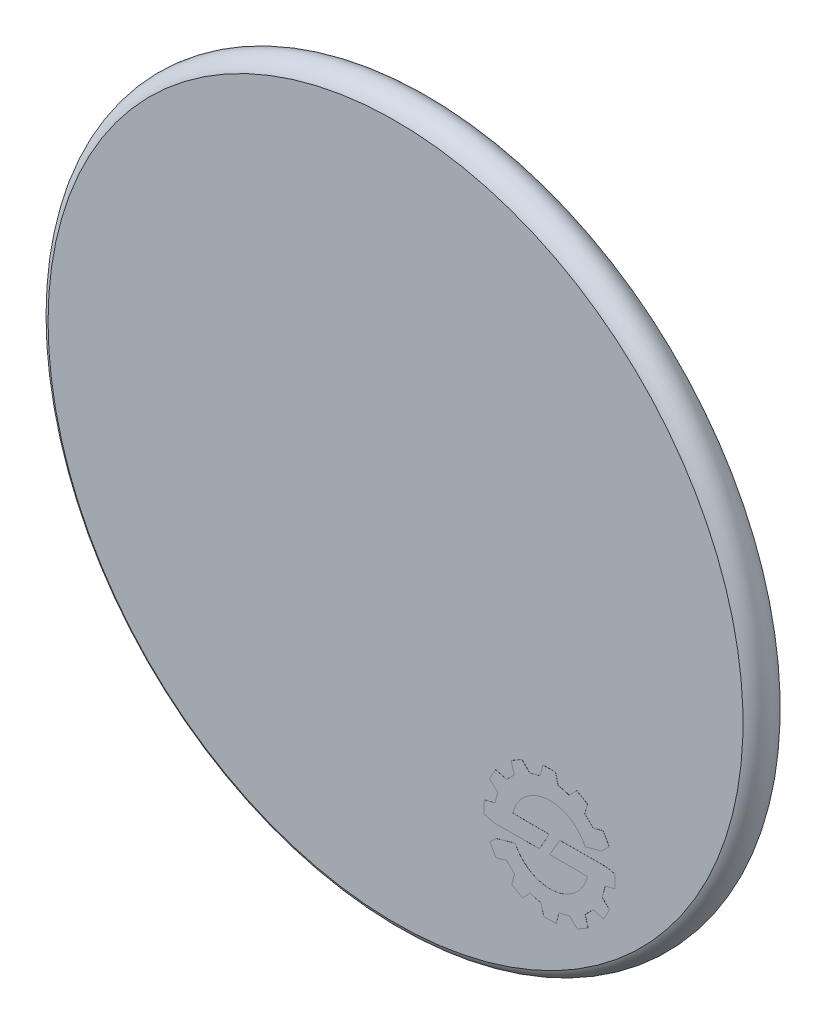
SolidWorks part; units mm, degrees
ref_plane "Front Plane" through (0, 0, 0) normal (0, 0, 1) x (1, 0, 0)
ref_plane "Top Plane" through (0, 0, 0) normal (0, 1, 0) x (1, 0, 0)
ref_plane "Right Plane" through (0, 0, 0) normal (1, 0, 0) x (0, 0, -1)
sketch "Sketch1" plane through (0, 0, 0) normal (0, 1, 0) x (1, 0, 0)
  line L0 (0, 0) -> (-40, 0)
  line L3 (-40, 0) -> (-42, 1.5)
  line L4 (0, 0) -> (0, -3)
  line L5 (0, -3) -> (-42, -3)
  line L6 (-42, -3) -> (-44.5, -3)
  line L8 (-44.5, 1.5) -> (-42, 1.5)
  arc A0 (-44.5, 1.5) -> (-44.5, -3) centre (-43.5625, -0.75) ccw
  dimension "D1" = 40
  dimension "D2" = 42
revolve "Revolve1" add sketch "Sketch1" angle 360 about L4
sketch "Sketch5" plane through (0, 0, 3) normal (0, 0, 1) x (1, 0, 0)
  line L0 (16.6947, -18.7297) -> (16.1934, -18.2222)
  line L1 (16.1934, -18.2222) -> (16.1083, -18.2709)
  line L2 (14.8898, -18.991) -> (14.8169, -19.0457)
  line L3 (14.8169, -19.0457) -> (14.8685, -19.2432)
  line L4 (15.1116, -20.0667) -> (15.221, -20.4222)
  line L5 (15.221, -20.4222) -> (14.8777, -20.7655)
  line L6 (12.1187, -22.2757) -> (12.0518, -22.4124)
  line L7 (12.0518, -22.4124) -> (12.3374, -22.6859)
  line L8 (12.1004, -26.8973) -> (12.617, -27.0189)
  line L9 (12.617, -27.0189) -> (15.4915, -27.0189)
  line L10 (24.1878, -23.6491) -> (24.2911, -23.8497)
  line L11 (24.2911, -23.8497) -> (24.4856, -23.798)
  line L12 (25.543, -23.5093) -> (26.3999, -23.2723)
  line L13 (26.3999, -23.2723) -> (26.886, -22.8014)
  line L14 (26.6186, -21.0056) -> (26.5609, -20.9326)
  line L15 (26.5609, -20.9326) -> (26.2145, -21.0329)
  line L16 (24.4734, -20.4404) -> (24.2364, -20.2277)
  line L17 (24.2364, -20.2277) -> (24.3914, -19.6808)
  line L18 (23.4221, -18.3013) -> (23.1942, -18.1706)
  line L19 (23.1942, -18.1706) -> (22.7202, -18.6659)
  line L20 (22.7202, -18.6659) -> (22.2462, -19.1612)
  line L21 (22.2462, -19.1612) -> (22.0669, -19.0943)
  line L22 (20.5294, -17.5963) -> (20.496, -17.4778)
  line L23 (20.496, -17.4778) -> (19.6938, -17.4778)
  line L24 (20.3805, -25.8885) -> (19.7515, -26.9885)
  line L25 (19.7515, -26.9885) -> (22.1641, -26.9885)
  line L26 (12.4438, -29.0486) -> (12.0822, -29.4102)
  line L27 (12.0822, -29.4102) -> (12.2189, -29.6351)
  line L28 (14.747, -30.8961) -> (15.2544, -31.4035)
  line L29 (15.2544, -31.4035) -> (15.1299, -31.8623)
  line L30 (16.1721, -33.4697) -> (16.2906, -33.5274)
  line L31 (16.2906, -33.5274) -> (16.4608, -33.3482)
  line L32 (16.9408, -32.8438) -> (17.2538, -32.5156)
  line L33 (17.2538, -32.5156) -> (17.5273, -32.6098)
  line L34 (20.3562, -34.2202) -> (20.5871, -34.2202)
  line L35 (20.5871, -34.2202) -> (20.7451, -33.567)
  line L36 (25.2057, -30.4403) -> (25.3029, -30.3218)
  line L37 (25.3029, -30.3218) -> (25.6007, -30.4069)
  line L38 (26.2692, -30.5892) -> (26.6399, -30.6894)
  line L39 (26.6399, -30.6894) -> (26.7888, -30.4281)
  line L40 (26.6916, -28.5928) -> (26.4485, -28.3649)
  line L41 (26.4485, -28.3649) -> (26.5731, -27.9882)
  line L42 (27.5089, -26.7606) -> (28.1166, -26.6087)
  line L43 (28.1166, -26.6087) -> (28.1166, -25.8034)
  line L44 (28.1166, -25.8034) -> (28.1166, -24.9982)
  line L45 (28.1166, -24.9982) -> (27.6153, -24.8706)
  line L46 (27.6153, -24.8706) -> (27.1139, -24.746)
  line L47 (27.1139, -24.746) -> (24.1209, -24.746)
  spline S0 degree 3 poles (18.8916, -17.4839) (18.8916, -17.49) (18.8126, -17.7999) (18.7184, -18.1767) knots 0 0 0 0 1 1 1 1
  spline S1 degree 3 poles (18.7184, -18.1767) (18.5239, -18.9424) (18.5756, -18.8603) (18.2262, -18.9393) knots 0 0 0 0 1 1 1 1
  spline S2 degree 3 poles (18.2262, -18.9393) (18.135, -18.9576) (17.8737, -19.0335) (17.6488, -19.1065) knots 0 0 0 0 1 1 1 1
  spline S3 degree 3 poles (17.6488, -19.1065) (17.424, -19.1794) (17.2295, -19.2402) (17.2174, -19.2402) knots 0 0 0 0 1 1 1 1
  spline S4 degree 3 poles (17.2174, -19.2402) (17.2052, -19.2402) (16.9682, -19.0123) (16.6947, -18.7297) knots 0 0 0 0 1 1 1 1
  spline S5 degree 3 poles (16.1083, -18.2709) (15.3881, -18.6871) (14.9476, -18.9485) (14.8898, -18.991) knots 0 0 0 0 1 1 1 1
  spline S6 degree 3 poles (14.8685, -19.2432) (14.9232, -19.4529) (14.9415, -19.5197) (15.1116, -20.0667) knots 0 0 0 0 1 1 1 1
  spline S7 degree 3 poles (14.8777, -20.7655) (14.6893, -20.9539) (14.4796, -21.1727) (14.4128, -21.2517) knots 0 0 0 0 1 1 1 1
  spline S8 degree 3 poles (14.4128, -21.2517) (14.3459, -21.3307) (14.27, -21.3975) (14.2456, -21.3975) knots 0 0 0 0 1 1 1 1
  spline S9 degree 3 poles (14.2456, -21.3975) (14.2213, -21.3975) (14.0573, -21.355) (13.881, -21.3064) knots 0 0 0 0 1 1 1 1
  spline S10 degree 3 poles (13.881, -21.3064) (13.2399, -21.121) (12.8418, -21.0268) (12.8175, -21.0511) knots 0 0 0 0 1 1 1 1
  spline S11 degree 3 poles (12.8175, -21.0511) (12.8054, -21.0663) (12.7324, -21.1879) (12.6595, -21.3216) knots 0 0 0 0 1 1 1 1
  spline S12 degree 3 poles (12.6595, -21.3216) (12.5836, -21.4553) (12.4468, -21.6953) (12.3557, -21.8533) knots 0 0 0 0 1 1 1 1
  spline S13 degree 3 poles (12.3557, -21.8533) (12.2645, -22.0113) (12.1582, -22.2028) (12.1187, -22.2757) knots 0 0 0 0 1 1 1 1
  spline S14 degree 3 poles (12.3374, -22.6859) (12.4924, -22.8378) (12.7324, -23.0687) (12.8722, -23.2024) knots 0 0 0 0 1 1 1 1
  spline S15 degree 3 poles (12.8722, -23.2024) (13.009, -23.3331) (13.1214, -23.4486) (13.1214, -23.4546) knots 0 0 0 0 1 1 1 1
  spline S16 degree 3 poles (13.1214, -23.4546) (13.1214, -23.4638) (13.0819, -23.5792) (13.0333, -23.716) knots 0 0 0 0 1 1 1 1
  spline S17 degree 3 poles (13.0333, -23.716) (12.9877, -23.8527) (12.9178, -24.1019) (12.8783, -24.269) knots 0 0 0 0 1 1 1 1
  spline S18 degree 3 poles (12.8783, -24.269) (12.8418, -24.4361) (12.8023, -24.6123) (12.7902, -24.6609) knots 0 0 0 0 1 1 1 1
  spline S19 degree 3 poles (12.7902, -24.6609) (12.7689, -24.7491) (12.7568, -24.7551) (12.3162, -24.8645) knots 0 0 0 0 1 1 1 1
  spline S20 degree 3 poles (12.3162, -24.8645) (12.064, -24.9253) (11.7571, -25.0013) (11.6325, -25.0316) knots 0 0 0 0 1 1 1 1
  spline S21 degree 3 poles (11.6325, -25.0316) (11.5079, -25.059) (11.3864, -25.0955) (11.3651, -25.1137) knots 0 0 0 0 1 1 1 1
  spline S22 degree 3 poles (11.3651, -25.1137) (11.3377, -25.135) (11.3286, -25.3234) (11.3317, -25.8916) knots 0 0 0 0 1 1 1 1
  spline S23 degree 3 poles (11.3317, -25.8916) (11.3317, -26.3018) (11.3469, -26.6603) (11.359, -26.6877) knots 0 0 0 0 1 1 1 1
  spline S24 degree 3 poles (11.359, -26.6877) (11.3742, -26.715) (11.4319, -26.7454) (11.4866, -26.7545) knots 0 0 0 0 1 1 1 1
  spline S25 degree 3 poles (11.4866, -26.7545) (11.5413, -26.7636) (11.8178, -26.8274) (12.1004, -26.8973) knots 0 0 0 0 1 1 1 1
  spline S26 degree 3 poles (15.4915, -27.0189) (17.7461, -27.0189) (18.3781, -27.0097) (18.4145, -26.9794) knots 0 0 0 0 1 1 1 1
  spline S27 degree 3 poles (18.4145, -26.9794) (18.4389, -26.9611) (18.5969, -26.7029) (18.764, -26.4112) knots 0 0 0 0 1 1 1 1
  spline S28 degree 3 poles (18.764, -26.4112) (18.9311, -26.1195) (19.2076, -25.6394) (19.3778, -25.3446) knots 0 0 0 0 1 1 1 1
  spline S29 degree 3 poles (19.3778, -25.3446) (19.5449, -25.0499) (19.6847, -24.7977) (19.6847, -24.7886) knots 0 0 0 0 1 1 1 1
  spline S30 degree 3 poles (19.6847, -24.7886) (19.6847, -24.7794) (18.6394, -24.7703) (17.3602, -24.7703) knots 0 0 0 0 1 1 1 1
  spline S31 degree 3 poles (17.3602, -24.7703) (15.139, -24.7703) (15.0357, -24.7673) (15.0357, -24.7156) knots 0 0 0 0 1 1 1 1
  spline S32 degree 3 poles (15.0357, -24.7156) (15.0357, -24.6458) (15.218, -24.1079) (15.3152, -23.8892) knots 0 0 0 0 1 1 1 1
  spline S33 degree 3 poles (15.3152, -23.8892) (16.1295, -22.0691) (18.0074, -20.8992) (19.9733, -20.9843) knots 0 0 0 0 1 1 1 1
  spline S34 degree 3 poles (19.9733, -20.9843) (21.4926, -21.0481) (22.7809, -21.7105) (23.7077, -22.8955) knots 0 0 0 0 1 1 1 1
  spline S35 degree 3 poles (23.7077, -22.8955) (23.8171, -23.0384) (23.9082, -23.1599) (23.9082, -23.169) knots 0 0 0 0 1 1 1 1
  spline S36 degree 3 poles (23.9082, -23.169) (23.9082, -23.1781) (23.9478, -23.245) (23.9964, -23.3179) knots 0 0 0 0 1 1 1 1
  spline S37 degree 3 poles (23.9964, -23.3179) (24.0419, -23.3908) (24.1301, -23.5397) (24.1878, -23.6491) knots 0 0 0 0 1 1 1 1
  spline S38 degree 3 poles (24.4856, -23.798) (24.595, -23.7706) (25.069, -23.64) (25.543, -23.5093) knots 0 0 0 0 1 1 1 1
  spline S39 degree 3 poles (26.886, -22.8014) (27.1534, -22.54) (27.3722, -22.3182) (27.3722, -22.3061) knots 0 0 0 0 1 1 1 1
  spline S40 degree 3 poles (27.3722, -22.3061) (27.3722, -22.2909) (27.2324, -22.0447) (27.0653, -21.7561) knots 0 0 0 0 1 1 1 1
  spline S41 degree 3 poles (27.0653, -21.7561) (26.8951, -21.4674) (26.7371, -21.197) (26.7159, -21.1545) knots 0 0 0 0 1 1 1 1
  spline S42 degree 3 poles (26.7159, -21.1545) (26.6916, -21.1119) (26.649, -21.0451) (26.6186, -21.0056) knots 0 0 0 0 1 1 1 1
  spline S43 degree 3 poles (26.2145, -21.0329) (26.0231, -21.0846) (25.7648, -21.1636) (25.6372, -21.2031) knots 0 0 0 0 1 1 1 1
  spline S44 degree 3 poles (25.6372, -21.2031) (25.5096, -21.2426) (25.385, -21.276) (25.3576, -21.276) knots 0 0 0 0 1 1 1 1
  spline S45 degree 3 poles (25.3576, -21.276) (25.3333, -21.276) (25.2513, -21.2122) (25.1784, -21.1332) knots 0 0 0 0 1 1 1 1
  spline S46 degree 3 poles (25.1784, -21.1332) (24.9596, -20.8962) (24.7256, -20.6652) (24.4734, -20.4404) knots 0 0 0 0 1 1 1 1
  spline S47 degree 3 poles (24.3914, -19.6808) (24.6071, -18.912) (24.6041, -18.9637) (24.4643, -18.8907) knots 0 0 0 0 1 1 1 1
  spline S48 degree 3 poles (24.4643, -18.8907) (24.4005, -18.8573) (24.1908, -18.7388) (23.9994, -18.6294) knots 0 0 0 0 1 1 1 1
  spline S49 degree 3 poles (23.9994, -18.6294) (23.808, -18.52) (23.5467, -18.3711) (23.4221, -18.3013) knots 0 0 0 0 1 1 1 1
  spline S50 degree 3 poles (22.0669, -19.0943) (21.8299, -19.0092) (21.3467, -18.8847) (21.1584, -18.8603) knots 0 0 0 0 1 1 1 1
  spline S51 degree 3 poles (21.1584, -18.8603) (20.815, -18.8148) (20.8363, -18.8421) (20.6935, -18.3043) knots 0 0 0 0 1 1 1 1
  spline S52 degree 3 poles (20.6935, -18.3043) (20.6236, -18.0399) (20.5658, -17.7999) (20.5658, -17.7695) knots 0 0 0 0 1 1 1 1
  spline S53 degree 3 poles (20.5658, -17.7695) (20.5658, -17.7391) (20.5506, -17.6601) (20.5294, -17.5963) knots 0 0 0 0 1 1 1 1
  spline S54 degree 3 poles (19.6938, -17.4778) (19.2562, -17.4778) (18.8946, -17.4808) (18.8916, -17.4839) knots 0 0 0 0 1 1 1 1
  spline S55 degree 3 poles (21.0702, -24.7673) (21.0368, -24.7794) (20.7542, -25.2413) (20.3805, -25.8885) knots 0 0 0 0 1 1 1 1
  spline S56 degree 3 poles (22.1641, -26.9885) (24.1453, -26.9885) (24.5767, -26.9946) (24.5767, -27.028) knots 0 0 0 0 1 1 1 1
  spline S57 degree 3 poles (24.5767, -27.028) (24.5767, -27.0523) (24.5433, -27.1829) (24.5008, -27.3197) knots 0 0 0 0 1 1 1 1
  spline S58 degree 3 poles (24.5008, -27.3197) (24.285, -28.0398) (23.8171, -28.8116) (23.2762, -29.3494) knots 0 0 0 0 1 1 1 1
  spline S59 degree 3 poles (23.2762, -29.3494) (22.5774, -30.0361) (21.8238, -30.4433) (20.8089, -30.6834) knots 0 0 0 0 1 1 1 1
  spline S60 degree 3 poles (20.8089, -30.6834) (20.3228, -30.7958) (19.5631, -30.814) (19.0466, -30.7259) knots 0 0 0 0 1 1 1 1
  spline S61 degree 3 poles (19.0466, -30.7259) (17.6124, -30.4767) (16.5306, -29.787) (15.7011, -28.5837) knots 0 0 0 0 1 1 1 1
  spline S62 degree 3 poles (15.7011, -28.5837) (15.6434, -28.4986) (15.5401, -28.3254) (15.4763, -28.1978) knots 0 0 0 0 1 1 1 1
  spline S63 degree 3 poles (15.4763, -28.1978) (15.4094, -28.0672) (15.3395, -27.9608) (15.3243, -27.9608) knots 0 0 0 0 1 1 1 1
  spline S64 degree 3 poles (15.3243, -27.9608) (15.3061, -27.9608) (15.1754, -27.9942) (15.0357, -28.0337) knots 0 0 0 0 1 1 1 1
  spline S65 degree 3 poles (15.0357, -28.0337) (14.8929, -28.0763) (14.3672, -28.2191) (13.8658, -28.3558) knots 0 0 0 0 1 1 1 1
  spline S66 degree 3 poles (13.8658, -28.3558) (13.3645, -28.4956) (12.9208, -28.6232) (12.8783, -28.6445) knots 0 0 0 0 1 1 1 1
  spline S67 degree 3 poles (12.8783, -28.6445) (12.8358, -28.6688) (12.6413, -28.8481) (12.4438, -29.0486) knots 0 0 0 0 1 1 1 1
  spline S68 degree 3 poles (12.2189, -29.6351) (12.3496, -29.8538) (12.5289, -30.1577) (12.6352, -30.3461) knots 0 0 0 0 1 1 1 1
  spline S69 degree 3 poles (12.6352, -30.3461) (12.6626, -30.3947) (12.7324, -30.5102) (12.7871, -30.6013) knots 0 0 0 0 1 1 1 1
  spline S70 degree 3 poles (12.7871, -30.6013) (12.8844, -30.7593) (12.8904, -30.7624) (13.0029, -30.7441) knots 0 0 0 0 1 1 1 1
  spline S71 degree 3 poles (13.0029, -30.7441) (13.0667, -30.735) (13.2247, -30.6925) (13.3553, -30.653) knots 0 0 0 0 1 1 1 1
  spline S72 degree 3 poles (13.3553, -30.653) (13.486, -30.6104) (13.7261, -30.5375) (13.8901, -30.4859) knots 0 0 0 0 1 1 1 1
  spline S73 degree 3 poles (13.8901, -30.4859) (14.0542, -30.4342) (14.2001, -30.3917) (14.2153, -30.3917) knots 0 0 0 0 1 1 1 1
  spline S74 degree 3 poles (14.2153, -30.3917) (14.2305, -30.3917) (14.4705, -30.6196) (14.747, -30.8961) knots 0 0 0 0 1 1 1 1
  spline S75 degree 3 poles (15.1299, -31.8623) (15.06, -32.1145) (14.9749, -32.4062) (14.9445, -32.5126) knots 0 0 0 0 1 1 1 1
  spline S76 degree 3 poles (14.9445, -32.5126) (14.8898, -32.6949) (14.8898, -32.7921) (14.9476, -32.7921) knots 0 0 0 0 1 1 1 1
  spline S77 degree 3 poles (14.9476, -32.7921) (14.9627, -32.7921) (15.0387, -32.8316) (15.1177, -32.8772) knots 0 0 0 0 1 1 1 1
  spline S78 degree 3 poles (15.1177, -32.8772) (15.3729, -33.0322) (16.0505, -33.4089) (16.1721, -33.4697) knots 0 0 0 0 1 1 1 1
  spline S79 degree 3 poles (16.4608, -33.3482) (16.5549, -33.2509) (16.7707, -33.023) (16.9408, -32.8438) knots 0 0 0 0 1 1 1 1
  spline S80 degree 3 poles (17.5273, -32.6098) (17.7795, -32.6949) (18.2687, -32.8195) (18.5361, -32.865) knots 0 0 0 0 1 1 1 1
  spline S81 degree 3 poles (18.5361, -32.865) (18.6303, -32.8833) (18.6485, -32.8985) (18.6667, -32.9835) knots 0 0 0 0 1 1 1 1
  spline S82 degree 3 poles (18.6667, -32.9835) (18.7123, -33.2145) (18.9676, -34.1777) (18.9919, -34.2081) knots 0 0 0 0 1 1 1 1
  spline S83 degree 3 poles (18.9919, -34.2081) (19.0101, -34.2324) (19.1833, -34.2415) (19.5722, -34.2324) knots 0 0 0 0 1 1 1 1
  spline S84 degree 3 poles (19.5722, -34.2324) (19.8761, -34.2263) (20.2286, -34.2233) (20.3562, -34.2202) knots 0 0 0 0 1 1 1 1
  spline S85 degree 3 poles (20.7451, -33.567) (20.8332, -33.2084) (20.9244, -32.9015) (20.9457, -32.8833) knots 0 0 0 0 1 1 1 1
  spline S86 degree 3 poles (20.9457, -32.8833) (20.9639, -32.8681) (21.055, -32.8377) (21.1462, -32.8225) knots 0 0 0 0 1 1 1 1
  spline S87 degree 3 poles (21.1462, -32.8225) (21.3802, -32.78) (22.0942, -32.5764) (22.1307, -32.546) knots 0 0 0 0 1 1 1 1
  spline S88 degree 3 poles (22.1307, -32.546) (22.1459, -32.5308) (22.1945, -32.5186) (22.2431, -32.5186) knots 0 0 0 0 1 1 1 1
  spline S89 degree 3 poles (22.2431, -32.5186) (22.31, -32.5186) (22.4133, -32.6068) (22.787, -32.9896) knots 0 0 0 0 1 1 1 1
  spline S90 degree 3 poles (22.787, -32.9896) (23.0423, -33.2479) (23.2732, -33.4606) (23.2975, -33.4606) knots 0 0 0 0 1 1 1 1
  spline S91 degree 3 poles (23.2975, -33.4606) (23.3248, -33.4606) (23.3735, -33.4424) (23.4069, -33.4181) knots 0 0 0 0 1 1 1 1
  spline S92 degree 3 poles (23.4069, -33.4181) (23.4403, -33.3968) (23.5163, -33.3512) (23.574, -33.3178) knots 0 0 0 0 1 1 1 1
  spline S93 degree 3 poles (23.574, -33.3178) (23.6895, -33.2509) (23.9721, -33.0869) (24.1361, -32.9896) knots 0 0 0 0 1 1 1 1
  spline S94 degree 3 poles (24.1361, -32.9896) (24.1939, -32.9562) (24.3306, -32.8772) (24.44, -32.8134) knots 0 0 0 0 1 1 1 1
  spline S95 degree 3 poles (24.44, -32.8134) (24.6648, -32.6827) (24.6679, -32.6706) (24.5767, -32.3698) knots 0 0 0 0 1 1 1 1
  spline S96 degree 3 poles (24.5767, -32.3698) (24.3944, -31.762) (24.3033, -31.44) (24.3033, -31.3913) knots 0 0 0 0 1 1 1 1
  spline S97 degree 3 poles (24.3033, -31.3913) (24.3033, -31.364) (24.3549, -31.2941) (24.4187, -31.2364) knots 0 0 0 0 1 1 1 1
  spline S98 degree 3 poles (24.4187, -31.2364) (24.598, -31.0753) (25.0994, -30.5709) (25.2057, -30.4403) knots 0 0 0 0 1 1 1 1
  spline S99 degree 3 poles (25.6007, -30.4069) (25.7648, -30.4524) (26.0656, -30.5345) (26.2692, -30.5892) knots 0 0 0 0 1 1 1 1
  spline S100 degree 3 poles (26.7888, -30.4281) (27.2871, -29.5439) (27.4026, -29.3312) (27.4026, -29.3039) knots 0 0 0 0 1 1 1 1
  spline S101 degree 3 poles (27.4026, -29.3039) (27.4026, -29.2765) (27.2659, -29.1367) (26.6916, -28.5928) knots 0 0 0 0 1 1 1 1
  spline S102 degree 3 poles (26.5731, -27.9882) (26.6429, -27.7815) (26.7311, -27.4595) (26.7675, -27.2771) knots 0 0 0 0 1 1 1 1
  spline S103 degree 3 poles (26.7675, -27.2771) (26.807, -27.0918) (26.8526, -26.9368) (26.8708, -26.9277) knots 0 0 0 0 1 1 1 1
  spline S104 degree 3 poles (26.8708, -26.9277) (26.886, -26.9216) (27.1747, -26.8457) (27.5089, -26.7606) knots 0 0 0 0 1 1 1 1
  spline S105 degree 3 poles (24.1209, -24.746) (22.4741, -24.746) (21.1006, -24.7551) (21.0702, -24.7673) knots 0 0 0 0 1 1 1 1
extrude "Boss-Extrude2" add sketch "Sketch5" along normal blind 0.01
sketch "Sketch6" plane through (0, 0, 0) normal (0, 0, -1) x (-1, 0, 0)
  line L0 (-8.609, 24.4061) -> (-8.5862, 24.048)
  line L1 (-8.5862, 24.048) -> (-7.7861, 23.5146)
  line L2 (-0.3185, 16.1308) -> (-1.0348, 16.1232)
  line L3 (-1.0348, 16.1232) -> (-1.1338, 16.5042)
  line L4 (-2.3454, -1.098) -> (-2.3378, -4.4508)
  line L5 (-2.3378, -4.4508) -> (-2.5892, -5.1671)
  line L6 (-0.9586, -8.8933) -> (-2.3378, -8.8704)
  line L7 (-2.3378, -8.8704) -> (-2.3606, -8.6418)
  line L8 (11.5382, -3.6965) -> (11.5916, -8.7409)
  line L9 (11.5916, -8.7409) -> (11.4316, -8.8247)
  line L10 (-17.052, -2.6449) -> (-15.9928, -2.6678)
  line L11 (-15.9928, -2.6678) -> (-16.0462, -2.302)
  line L12 (-8.228, -0.6637) -> (-8.2052, -5.9748)
  line L13 (-8.2052, -5.9748) -> (-7.588, -5.9977)
  line L14 (2.8514, -2.6601) -> (3.8725, -2.6601)
  line L15 (3.8725, -2.6601) -> (3.8725, -2.4315)
  spline S0 degree 3 poles (9.7628, 31.4698) (6.9281, 31.1117) (3.6211, 29.3515) (1.7542, 27.2179) knots 0 0 0 0 1 1 1 1
  spline S1 degree 3 poles (1.7542, 27.2179) (0.5654, 25.8691) (-0.1356, 24.7109) (-0.6461, 23.286) knots 0 0 0 0 1 1 1 1
  spline S2 degree 3 poles (-0.6461, 23.286) (-1.1186, 21.9829) (-1.1795, 21.5943) (-1.1872, 20.1846) knots 0 0 0 0 1 1 1 1
  spline S3 degree 3 poles (-1.1872, 20.1846) (-1.1948, 18.4854) (-1.2938, 18.5692) (0.2302, 18.8968) knots 0 0 0 0 1 1 1 1
  spline S4 degree 3 poles (0.2302, 18.8968) (2.9124, 19.476) (4.8098, 20.337) (6.5243, 21.7467) knots 0 0 0 0 1 1 1 1
  spline S5 degree 3 poles (6.5243, 21.7467) (8.4369, 23.3317) (10.2733, 26.4102) (10.9667, 29.1838) knots 0 0 0 0 1 1 1 1
  spline S6 degree 3 poles (10.9667, 29.1838) (11.3858, 30.8526) (11.2639, 31.3098) (10.3876, 31.5003) knots 0 0 0 0 1 1 1 1
  spline S7 degree 3 poles (10.3876, 31.5003) (10.3038, 31.5156) (10.0219, 31.5079) (9.7628, 31.4698) knots 0 0 0 0 1 1 1 1
  spline S8 degree 3 poles (-8.0452, 25.6101) (-8.4795, 25.2062) (-8.6395, 24.8709) (-8.609, 24.4061) knots 0 0 0 0 1 1 1 1
  spline S9 degree 3 poles (-7.7861, 23.5146) (-6.1402, 22.4173) (-4.7762, 20.8018) (-3.8618, 18.874) knots 0 0 0 0 1 1 1 1
  spline S10 degree 3 poles (-3.8618, 18.874) (-3.4351, 17.9824) (-2.8712, 16.4051) (-2.9474, 16.3289) knots 0 0 0 0 1 1 1 1
  spline S11 degree 3 poles (-2.9474, 16.3289) (-3.016, 16.2527) (-3.8237, 16.5499) (-4.9286, 17.0376) knots 0 0 0 0 1 1 1 1
  spline S12 degree 3 poles (-4.9286, 17.0376) (-7.5041, 18.1958) (-9.4091, 18.592) (-11.8247, 18.5006) knots 0 0 0 0 1 1 1 1
  spline S13 degree 3 poles (-11.8247, 18.5006) (-14.6898, 18.3787) (-16.9682, 17.5633) (-19.2999, 15.8107) knots 0 0 0 0 1 1 1 1
  spline S14 degree 3 poles (-19.2999, 15.8107) (-22.5155, 13.38) (-24.7253, 9.4709) (-25.4797, 4.8608) knots 0 0 0 0 1 1 1 1
  spline S15 degree 3 poles (-25.4797, 4.8608) (-25.7083, 3.474) (-25.7312, -0.3056) (-25.5178, -1.9362) knots 0 0 0 0 1 1 1 1
  spline S16 degree 3 poles (-25.5178, -1.9362) (-25.0987, -5.1214) (-24.3139, -8.1008) (-23.0642, -11.1717) knots 0 0 0 0 1 1 1 1
  spline S17 degree 3 poles (-23.0642, -11.1717) (-22.2946, -13.0767) (-20.5801, -16.1628) (-18.9341, -18.6317) knots 0 0 0 0 1 1 1 1
  spline S18 degree 3 poles (-18.9341, -18.6317) (-16.9377, -21.6263) (-14.3621, -23.9047) (-11.8552, -24.9105) knots 0 0 0 0 1 1 1 1
  spline S19 degree 3 poles (-11.8552, -24.9105) (-11.0322, -25.2306) (-11.0093, -25.2382) (-9.6911, -25.3068) knots 0 0 0 0 1 1 1 1
  spline S20 degree 3 poles (-9.6911, -25.3068) (-8.4795, -25.3754) (-8.289, -25.3677) (-7.6108, -25.2306) knots 0 0 0 0 1 1 1 1
  spline S21 degree 3 poles (-7.6108, -25.2306) (-7.1917, -25.1391) (-6.2545, -24.8343) (-5.4696, -24.5372) knots 0 0 0 0 1 1 1 1
  spline S22 degree 3 poles (-5.4696, -24.5372) (-4.7, -24.24) (-3.6637, -23.8895) (-3.1684, -23.7599) knots 0 0 0 0 1 1 1 1
  spline S23 degree 3 poles (-3.1684, -23.7599) (-2.3454, -23.5466) (-2.1244, -23.5161) (-0.8138, -23.4856) knots 0 0 0 0 1 1 1 1
  spline S24 degree 3 poles (-0.8138, -23.4856) (0.9007, -23.4399) (0.9769, -23.4551) (3.5449, -24.3467) knots 0 0 0 0 1 1 1 1
  spline S25 degree 3 poles (3.5449, -24.3467) (5.968, -25.1772) (6.4786, -25.2915) (7.873, -25.2915) knots 0 0 0 0 1 1 1 1
  spline S26 degree 3 poles (7.873, -25.2915) (9.2218, -25.2915) (9.6485, -25.2077) (10.7229, -24.7277) knots 0 0 0 0 1 1 1 1
  spline S27 degree 3 poles (10.7229, -24.7277) (13.9538, -23.2951) (16.9637, -19.6985) (20.1869, -13.4424) knots 0 0 0 0 1 1 1 1
  spline S28 degree 3 poles (20.1869, -13.4424) (21.8786, -10.1506) (22.7549, -7.6817) (23.4483, -4.2984) knots 0 0 0 0 1 1 1 1
  spline S29 degree 3 poles (23.4483, -4.2984) (24.5608, 1.1727) (24.1112, 6.4991) (22.2062, 10.4158) knots 0 0 0 0 1 1 1 1
  spline S30 degree 3 poles (22.2062, 10.4158) (20.1336, 14.6601) (16.7579, 17.3119) (12.2164, 18.2644) knots 0 0 0 0 1 1 1 1
  spline S31 degree 3 poles (12.2164, 18.2644) (11.3249, 18.4549) (11.0658, 18.4777) (9.6637, 18.4777) knots 0 0 0 0 1 1 1 1
  spline S32 degree 3 poles (9.6637, 18.4777) (8.2464, 18.4777) (8.0102, 18.4625) (7.111, 18.272) knots 0 0 0 0 1 1 1 1
  spline S33 degree 3 poles (7.111, 18.272) (6.0595, 18.051) (4.5202, 17.5481) (2.7829, 16.8699) knots 0 0 0 0 1 1 1 1
  spline S34 degree 3 poles (2.7829, 16.8699) (1.4113, 16.3365) (0.5959, 16.1384) (-0.3185, 16.1308) knots 0 0 0 0 1 1 1 1
  spline S35 degree 3 poles (-1.1338, 16.5042) (-1.3472, 17.3119) (-1.7968, 18.6682) (-2.0787, 19.3845) knots 0 0 0 0 1 1 1 1
  spline S36 degree 3 poles (-2.0787, 19.3845) (-3.2293, 22.2801) (-5.1191, 24.749) (-6.9098, 25.6863) knots 0 0 0 0 1 1 1 1
  spline S37 degree 3 poles (-6.9098, 25.6863) (-7.4889, 25.9911) (-7.6413, 25.9758) (-8.0452, 25.6101) knots 0 0 0 0 1 1 1 1
  spline S38 degree 3 poles (-15.2613, 7.4973) (-15.1089, 7.3602) (-14.9946, 6.9334) (-14.5679, 4.8075) knots 0 0 0 0 1 1 1 1
  spline S39 degree 3 poles (-14.5679, 4.8075) (-14.324, 3.5883) (-13.4706, -0.5646) (-12.8229, -3.6507) knots 0 0 0 0 1 1 1 1
  spline S40 degree 3 poles (-12.8229, -3.6507) (-11.939, -7.9103) (-11.9009, -8.1008) (-11.9009, -8.4285) knots 0 0 0 0 1 1 1 1
  spline S41 degree 3 poles (-11.9009, -8.4285) (-11.9009, -8.5885) (-11.939, -8.7638) (-11.9923, -8.8171) knots 0 0 0 0 1 1 1 1
  spline S42 degree 3 poles (-11.9923, -8.8171) (-12.099, -8.9238) (-14.7584, -8.9466) (-14.827, -8.8476) knots 0 0 0 0 1 1 1 1
  spline S43 degree 3 poles (-14.827, -8.8476) (-14.8498, -8.8095) (-15.0022, -8.1084) (-15.1699, -7.2855) knots 0 0 0 0 1 1 1 1
  spline S44 degree 3 poles (-15.1699, -7.2855) (-15.3299, -6.4701) (-15.4823, -5.7691) (-15.5051, -5.731) knots 0 0 0 0 1 1 1 1
  spline S45 degree 3 poles (-15.5051, -5.731) (-15.528, -5.6929) (-16.2595, -5.6624) (-17.1206, -5.67) knots 0 0 0 0 1 1 1 1
  spline S46 degree 3 poles (-17.1206, -5.67) (-18.8732, -5.6777) (-18.7894, -5.6472) (-18.8732, -6.2339) knots 0 0 0 0 1 1 1 1
  spline S47 degree 3 poles (-18.8732, -6.2339) (-18.9722, -6.935) (-19.2999, -8.5733) (-19.3685, -8.7333) knots 0 0 0 0 1 1 1 1
  spline S48 degree 3 poles (-19.3685, -8.7333) (-19.4371, -8.9085) (-19.4599, -8.9085) (-20.8087, -8.9085) knots 0 0 0 0 1 1 1 1
  spline S49 degree 3 poles (-20.8087, -8.9085) (-22.4698, -8.9085) (-22.4165, -8.939) (-22.2412, -8.0856) knots 0 0 0 0 1 1 1 1
  spline S50 degree 3 poles (-22.2412, -8.0856) (-22.1726, -7.7655) (-21.8907, -6.4549) (-21.624, -5.1747) knots 0 0 0 0 1 1 1 1
  spline S51 degree 3 poles (-21.624, -5.1747) (-21.3497, -3.8946) (-20.7706, -1.0523) (-20.321, 1.1499) knots 0 0 0 0 1 1 1 1
  spline S52 degree 3 poles (-20.321, 1.1499) (-19.3228, 6.1257) (-19.0637, 7.3373) (-18.9722, 7.4516) knots 0 0 0 0 1 1 1 1
  spline S53 degree 3 poles (-18.9722, 7.4516) (-18.8656, 7.5811) (-18.6446, 7.604) (-16.9606, 7.6192) knots 0 0 0 0 1 1 1 1
  spline S54 degree 3 poles (-16.9606, 7.6192) (-15.5966, 7.6269) (-15.4061, 7.6116) (-15.2613, 7.4973) knots 0 0 0 0 1 1 1 1
  spline S55 degree 3 poles (-5.9573, 7.4516) (-4.6466, 7.063) (-3.6027, 6.1943) (-3.0236, 4.998) knots 0 0 0 0 1 1 1 1
  spline S56 degree 3 poles (-3.0236, 4.998) (-2.4292, 3.7788) (-2.3454, 3.0244) (-2.3454, -1.098) knots 0 0 0 0 1 1 1 1
  spline S57 degree 3 poles (-2.5892, -5.1671) (-3.3893, -7.4531) (-4.5933, -8.4894) (-6.8488, -8.8247) knots 0 0 0 0 1 1 1 1
  spline S58 degree 3 poles (-6.8488, -8.8247) (-7.146, -8.8704) (-8.1823, -8.9085) (-9.1424, -8.9085) knots 0 0 0 0 1 1 1 1
  spline S59 degree 3 poles (-9.1424, -8.9085) (-10.5217, -8.9085) (-10.9103, -8.8857) (-11.0322, -8.8019) knots 0 0 0 0 1 1 1 1
  spline S60 degree 3 poles (-11.0322, -8.8019) (-11.177, -8.6952) (-11.177, -8.5123) (-11.1998, -0.6561) knots 0 0 0 0 1 1 1 1
  spline S61 degree 3 poles (-11.1998, -0.6561) (-11.2151, 6.7963) (-11.2075, 7.3906) (-11.0932, 7.5126) knots 0 0 0 0 1 1 1 1
  spline S62 degree 3 poles (-11.0932, 7.5126) (-10.9712, 7.6269) (-10.7426, 7.6345) (-8.67, 7.604) knots 0 0 0 0 1 1 1 1
  spline S63 degree 3 poles (-8.67, 7.604) (-6.8564, 7.5811) (-6.2849, 7.5507) (-5.9573, 7.4516) knots 0 0 0 0 1 1 1 1
  spline S64 degree 3 poles (4.6955, 7.4973) (4.8555, 7.3602) (4.8707, 7.2763) (6.3414, 0.1974) knots 0 0 0 0 1 1 1 1
  spline S65 degree 3 poles (6.3414, 0.1974) (6.5319, -0.7247) (6.9891, -2.9497) (7.3701, -4.7556) knots 0 0 0 0 1 1 1 1
  spline S66 degree 3 poles (7.3701, -4.7556) (7.7435, -6.554) (8.0711, -8.1694) (8.094, -8.337) knots 0 0 0 0 1 1 1 1
  spline S67 degree 3 poles (8.094, -8.337) (8.1778, -8.8628) (8.1626, -8.8704) (6.5852, -8.8933) knots 0 0 0 0 1 1 1 1
  spline S68 degree 3 poles (6.5852, -8.8933) (5.2365, -8.9162) (5.1755, -8.9085) (5.0993, -8.7638) knots 0 0 0 0 1 1 1 1
  spline S69 degree 3 poles (5.0993, -8.7638) (5.0536, -8.6799) (4.8936, -7.9789) (4.7412, -7.2169) knots 0 0 0 0 1 1 1 1
  spline S70 degree 3 poles (4.7412, -7.2169) (4.5888, -6.4473) (4.4364, -5.792) (4.3983, -5.7539) knots 0 0 0 0 1 1 1 1
  spline S71 degree 3 poles (4.3983, -5.7539) (4.3221, -5.67) (1.2665, -5.6929) (1.1827, -5.7767) knots 0 0 0 0 1 1 1 1
  spline S72 degree 3 poles (1.1827, -5.7767) (1.1522, -5.8072) (0.9998, -6.4854) (0.855, -7.2779) knots 0 0 0 0 1 1 1 1
  spline S73 degree 3 poles (0.855, -7.2779) (0.7102, -8.0627) (0.5502, -8.7561) (0.5045, -8.8095) knots 0 0 0 0 1 1 1 1
  spline S74 degree 3 poles (0.5045, -8.8095) (0.4435, -8.8857) (0.1082, -8.9085) (-0.9586, -8.8933) knots 0 0 0 0 1 1 1 1
  spline S75 degree 3 poles (-2.3606, -8.6418) (-2.3759, -8.5123) (-2.1016, -7.095) (-1.7663, -5.4795) knots 0 0 0 0 1 1 1 1
  spline S76 degree 3 poles (-1.7663, -5.4795) (-1.4234, -3.8641) (-0.73, -0.557) (-0.2347, 1.8738) knots 0 0 0 0 1 1 1 1
  spline S77 degree 3 poles (-0.2347, 1.8738) (0.2683, 4.3045) (0.7331, 6.5601) (0.8017, 6.8877) knots 0 0 0 0 1 1 1 1
  spline S78 degree 3 poles (0.8017, 6.8877) (0.9007, 7.3602) (0.9617, 7.5049) (1.0836, 7.5507) knots 0 0 0 0 1 1 1 1
  spline S79 degree 3 poles (1.0836, 7.5507) (1.175, 7.5888) (1.9828, 7.6192) (2.8895, 7.6192) knots 0 0 0 0 1 1 1 1
  spline S80 degree 3 poles (2.8895, 7.6192) (4.3602, 7.6269) (4.5583, 7.6116) (4.6955, 7.4973) knots 0 0 0 0 1 1 1 1
  spline S81 degree 3 poles (12.5441, 7.4973) (12.7193, 7.3449) (12.9403, 6.5067) (14.3119, 0.6546) knots 0 0 0 0 1 1 1 1
  spline S82 degree 3 poles (14.3119, 0.6546) (14.5329, -0.2675) (14.7386, -1.0676) (14.7691, -1.1285) knots 0 0 0 0 1 1 1 1
  spline S83 degree 3 poles (14.7691, -1.1285) (14.8072, -1.2047) (14.8606, -1.0828) (14.9215, -0.7856) knots 0 0 0 0 1 1 1 1
  spline S84 degree 3 poles (14.9215, -0.7856) (14.9672, -0.5418) (15.4016, 1.3708) (15.8816, 3.4587) knots 0 0 0 0 1 1 1 1
  spline S85 degree 3 poles (15.8816, 3.4587) (16.3617, 5.5466) (16.7503, 7.2992) (16.7503, 7.3678) knots 0 0 0 0 1 1 1 1
  spline S86 degree 3 poles (16.7503, 7.3678) (16.7503, 7.5888) (17.1389, 7.6345) (18.8839, 7.6116) knots 0 0 0 0 1 1 1 1
  spline S87 degree 3 poles (18.8839, 7.6116) (20.2098, 7.5964) (20.6441, 7.5659) (20.7356, 7.4821) knots 0 0 0 0 1 1 1 1
  spline S88 degree 3 poles (20.7356, 7.4821) (20.8575, 7.3906) (20.8651, 6.7201) (20.8651, -0.6866) knots 0 0 0 0 1 1 1 1
  spline S89 degree 3 poles (20.8651, -0.6866) (20.8651, -8.5809) (20.8651, -8.7561) (20.7203, -8.8323) knots 0 0 0 0 1 1 1 1
  spline S90 degree 3 poles (20.7203, -8.8323) (20.5222, -8.9314) (18.4648, -8.9314) (18.2667, -8.8323) knots 0 0 0 0 1 1 1 1
  spline S91 degree 3 poles (18.2667, -8.8323) (18.1295, -8.7561) (18.1219, -8.6114) (18.1219, -3.5745) knots 0 0 0 0 1 1 1 1
  spline S92 degree 3 poles (18.1219, -3.5745) (18.1219, -0.7247) (18.0914, 1.6071) (18.061, 1.6071) knots 0 0 0 0 1 1 1 1
  spline S93 degree 3 poles (18.061, 1.6071) (18.0229, 1.6071) (17.9467, 1.3785) (17.8781, 1.0965) knots 0 0 0 0 1 1 1 1
  spline S94 degree 3 poles (17.8781, 1.0965) (17.8171, 0.807) (17.4971, -0.397) (17.177, -1.5933) knots 0 0 0 0 1 1 1 1
  spline S95 degree 3 poles (17.177, -1.5933) (16.8494, -2.7897) (16.3312, -4.7785) (16.0112, -6.0129) knots 0 0 0 0 1 1 1 1
  spline S96 degree 3 poles (16.0112, -6.0129) (15.6988, -7.2474) (15.3787, -8.4056) (15.3025, -8.5809) knots 0 0 0 0 1 1 1 1
  spline S97 degree 3 poles (15.3025, -8.5809) (15.1654, -8.8857) (15.1425, -8.9085) (14.8529, -8.9085) knots 0 0 0 0 1 1 1 1
  spline S98 degree 3 poles (14.8529, -8.9085) (14.6929, -8.9085) (14.5024, -8.8857) (14.4338, -8.8628) knots 0 0 0 0 1 1 1 1
  spline S99 degree 3 poles (14.4338, -8.8628) (14.2967, -8.8095) (14.0452, -8.0322) (13.7023, -6.5921) knots 0 0 0 0 1 1 1 1
  spline S100 degree 3 poles (13.7023, -6.5921) (13.5728, -6.0587) (13.1765, -4.6185) (12.826, -3.3917) knots 0 0 0 0 1 1 1 1
  spline S101 degree 3 poles (12.826, -3.3917) (12.4755, -2.1725) (12.0488, -0.6256) (11.8735, 0.045) knots 0 0 0 0 1 1 1 1
  spline S102 degree 3 poles (11.8735, 0.045) (11.7059, 0.7079) (11.5459, 1.2718) (11.523, 1.2946) knots 0 0 0 0 1 1 1 1
  spline S103 degree 3 poles (11.523, 1.2946) (11.5001, 1.3175) (11.5078, -0.9304) (11.5382, -3.6965) knots 0 0 0 0 1 1 1 1
  spline S104 degree 3 poles (11.4316, -8.8247) (11.1877, -8.9543) (9.1227, -8.939) (8.9322, -8.8019) knots 0 0 0 0 1 1 1 1
  spline S105 degree 3 poles (8.9322, -8.8019) (8.7874, -8.6952) (8.7874, -8.5199) (8.7874, -0.6408) knots 0 0 0 0 1 1 1 1
  spline S106 degree 3 poles (8.7874, -0.6408) (8.7874, 7.2382) (8.7874, 7.4135) (8.9322, 7.5202) knots 0 0 0 0 1 1 1 1
  spline S107 degree 3 poles (8.9322, 7.5202) (9.0541, 7.604) (9.4275, 7.6269) (10.7381, 7.6269) knots 0 0 0 0 1 1 1 1
  spline S108 degree 3 poles (10.7381, 7.6269) (12.2012, 7.6269) (12.4069, 7.6116) (12.5441, 7.4973) knots 0 0 0 0 1 1 1 1
  spline S109 degree 3 poles (-17.2349, 3.2454) (-17.2349, 3.0396) (-17.7454, -0.1379) (-17.9283, -1.0752) knots 0 0 0 0 1 1 1 1
  spline S110 degree 3 poles (-17.9283, -1.0752) (-18.0578, -1.7381) (-18.1493, -2.3553) (-18.134, -2.4468) knots 0 0 0 0 1 1 1 1
  spline S111 degree 3 poles (-18.134, -2.4468) (-18.1112, -2.6144) (-18.0883, -2.622) (-17.052, -2.6449) knots 0 0 0 0 1 1 1 1
  spline S112 degree 3 poles (-16.0462, -2.302) (-16.069, -2.1039) (-16.2443, -1.1438) (-16.4272, -0.1836) knots 0 0 0 0 1 1 1 1
  spline S113 degree 3 poles (-16.4272, -0.1836) (-16.8691, 2.1024) (-17.0825, 3.2149) (-17.0825, 3.253) knots 0 0 0 0 1 1 1 1
  spline S114 degree 3 poles (-17.0825, 3.253) (-17.0825, 3.2682) (-17.113, 3.2835) (-17.1587, 3.2835) knots 0 0 0 0 1 1 1 1
  spline S115 degree 3 poles (-17.1587, 3.2835) (-17.1968, 3.2835) (-17.2349, 3.2682) (-17.2349, 3.2454) knots 0 0 0 0 1 1 1 1
  spline S116 degree 3 poles (-8.1137, 4.6855) (-8.2357, 4.6474) (-8.2433, 4.3426) (-8.228, -0.6637) knots 0 0 0 0 1 1 1 1
  spline S117 degree 3 poles (-7.588, -5.9977) (-6.7421, -6.0282) (-6.2392, -5.8377) (-5.7744, -5.3195) knots 0 0 0 0 1 1 1 1
  spline S118 degree 3 poles (-5.7744, -5.3195) (-5.18, -4.6566) (-5.1724, -4.6109) (-5.1343, -1.3343) knots 0 0 0 0 1 1 1 1
  spline S119 degree 3 poles (-5.1343, -1.3343) (-5.1038, 2.2395) (-5.1953, 3.1692) (-5.683, 3.8778) knots 0 0 0 0 1 1 1 1
  spline S120 degree 3 poles (-5.683, 3.8778) (-6.0335, 4.3807) (-6.5593, 4.6322) (-7.367, 4.6855) knots 0 0 0 0 1 1 1 1
  spline S121 degree 3 poles (-7.367, 4.6855) (-7.7023, 4.7008) (-8.0375, 4.7008) (-8.1137, 4.6855) knots 0 0 0 0 1 1 1 1
  spline S122 degree 3 poles (2.699, 3.1234) (2.6686, 3.0244) (2.5314, 2.1862) (2.3866, 1.2642) knots 0 0 0 0 1 1 1 1
  spline S123 degree 3 poles (2.3866, 1.2642) (2.2418, 0.3421) (2.0361, -0.8847) (1.9294, -1.4714) knots 0 0 0 0 1 1 1 1
  spline S124 degree 3 poles (1.9294, -1.4714) (1.8304, -2.0505) (1.7618, -2.5535) (1.7846, -2.5916) knots 0 0 0 0 1 1 1 1
  spline S125 degree 3 poles (1.7846, -2.5916) (1.8075, -2.6297) (2.2876, -2.6601) (2.8514, -2.6601) knots 0 0 0 0 1 1 1 1
  spline S126 degree 3 poles (3.8725, -2.4315) (3.8725, -2.302) (3.7049, -1.3343) (3.4991, -0.2751) knots 0 0 0 0 1 1 1 1
  spline S127 degree 3 poles (3.4991, -0.2751) (3.2934, 0.7765) (3.0648, 1.9881) (2.9962, 2.4072) knots 0 0 0 0 1 1 1 1
  spline S128 degree 3 poles (2.9962, 2.4072) (2.8591, 3.2073) (2.7676, 3.4282) (2.699, 3.1234) knots 0 0 0 0 1 1 1 1
extrude "Boss-Extrude3" add sketch "Sketch6" along normal blind 0.01 contours S36 S37 S8 L0 L1 S9 S10 S11 S12 S13 S14 S15 S16 S17 S18 S19 S20 S21 S22 S23 S24 S25 S26 S27 S28 S29 S30 S31 S32 S33 S34 L2 L3 S35 S62 S63 S55 S56 L4 L5 S57 S58 S59 S60 S61 S53 S54 S38 S39 | S6 S7 S0 S1 S2 S3 S4 S5 | S120 S121 S116 L12 L13 S117 S118 S119 | S114 S115 S109 S110 S111 L10 L11 S112 S113 | S126 S127 S128 S122 S123 S124 S125 L14 L15
